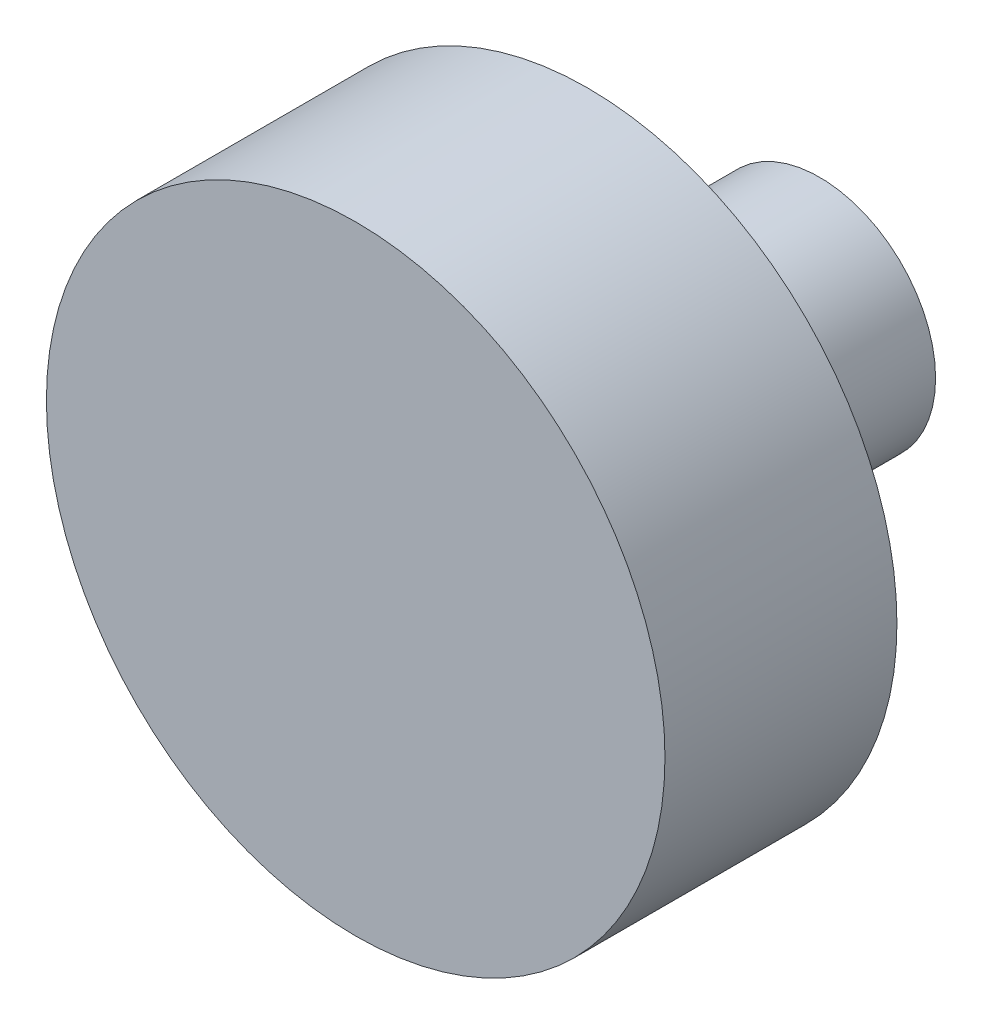
SolidWorks part; units mm, degrees
ref_plane "Front Plane" through (0, 0, 0) normal (0, 0, 1) x (1, 0, 0)
ref_plane "Top Plane" through (0, 0, 0) normal (0, 1, 0) x (1, 0, 0)
ref_plane "Right Plane" through (0, 0, 0) normal (1, 0, 0) x (0, 0, -1)
sketch "Sketch1" plane through (0, 0, 0) normal (0, 0, 1) x (1, 0, 0)
  circle A0 centre (0, 0) radius 101.6
extrude "Boss-Extrude1" add sketch "Sketch1" along normal blind 76.2
sketch "Sketch2" plane through (0, 0, 0) normal (0, 0, 1) x (1, 0, 0)
  circle A0 centre (0, 0) radius 38.1
extrude "Boss-Extrude2" add sketch "Sketch2" along normal blind 76.2
extrude "Boss-Extrude3" add sketch "Sketch2<3>" against normal blind 76.2
sketch "Sketch2<3>" plane through (0, 0, 0) normal (0, 0, 1) x (1, 0, 0) same geometry as "Sketch2"
